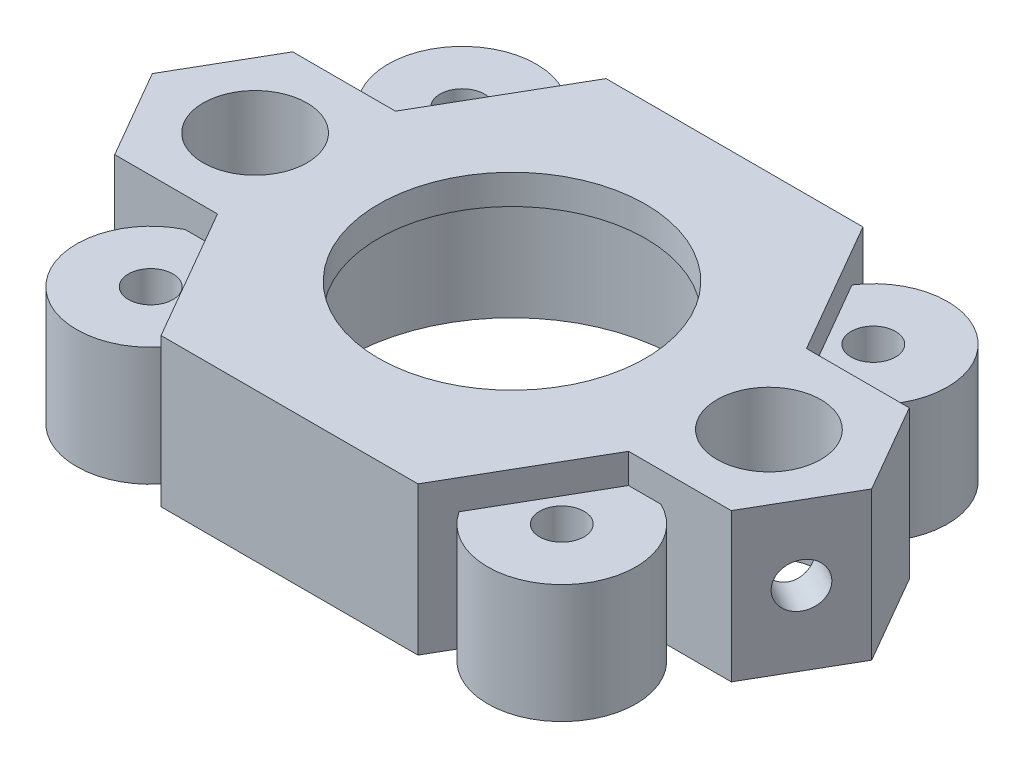
SolidWorks part; units mm, degrees
ref_plane "Front Plane" through (0, 0, 0) normal (0, 0, 1) x (1, 0, 0)
ref_plane "Top Plane" through (0, 0, 0) normal (0, 1, 0) x (1, 0, 0)
ref_plane "Right Plane" through (0, 0, 0) normal (1, 0, 0) x (0, 0, -1)
sketch "Sketch1" plane through (0, 0, 0) normal (0, 1, 0) x (1, 0, 0)
  line L0 (0, 0) -> (17.3205, 0) construction
  line L1 (17.3205, 0) -> (15.5705, 3.0311) construction
  line L2 (8.6603, 15) -> (-8.6603, 15)
  line L3 (-8.6603, 15) -> (-9.6753, 13.2419)
  line L4 (-9.6753, -13.2419) -> (-8.6603, -15)
  line L5 (-8.6603, -15) -> (8.6603, -15)
  line L6 (8.6603, -15) -> (9.6753, -13.2419)
  line L7 (0, 15) -> (0, -15) construction
  line L8 (24.2487, 0) -> (20.7846, 6)
  line L9 (20.7846, 6) -> (16.0359, 6)
  line L10 (12.1244, 3) -> (11.064, 1.1634)
  line L11 (11.064, -1.1634) -> (12.1244, -3) construction
  line L12 (16.0359, -6) -> (20.7846, -6)
  line L13 (20.7846, -6) -> (24.2487, 0)
  line L14 (-20.7846, -6) -> (-24.2487, 0)
  line L15 (-16.0359, -6) -> (-20.7846, -6)
  line L16 (-11.064, -1.1634) -> (-13.8564, -6) construction
  line L17 (-13.8564, 6) -> (-11.064, 1.1634) construction
  line L18 (-20.7846, 6) -> (-16.0359, 6)
  line L19 (-24.2487, 0) -> (-20.7846, 6)
  line L20 (-13.8564, 6) -> (-15.5705, 3.0311) construction
  line L21 (-15.5705, 3.0311) -> (-17.3205, 0) construction
  line L22 (-17.3205, 0) -> (-15.5705, -3.0311) construction
  line L23 (-11.064, 1.1634) -> (-10.3923, 0) construction
  line L24 (-10.3923, 0) -> (-11.064, -1.1634) construction
  line L25 (-15.5705, -3.0311) -> (-13.8564, -6) construction
  line L26 (11.064, 1.1634) -> (10.3923, 0) construction
  line L27 (10.3923, 0) -> (11.064, -1.1634) construction
  line L28 (12.1244, -3) -> (13.8564, -6) construction
  line L29 (15.5705, 3.0311) -> (14.3205, 5.1962) construction
  line L30 (9.6753, 13.2419) -> (8.6603, 15)
  line L31 (14.3205, -5.1962) -> (15.5705, -3.0311) construction
  line L32 (15.5705, -3.0311) -> (17.3205, 0) construction
  line L33 (13.8564, -6) -> (14.3205, -5.1962) construction
  line L34 (13.8564, 6) -> (12.1244, 3) construction
  line L35 (14.3205, 5.1962) -> (13.8564, 6) construction
  line L36 (-13.8564, 6) -> (-13.8564, 15) construction
  line L37 (-13.8564, 15) -> (-8.6603, 15) construction
  line L38 (-9.6753, 13.2419) -> (-13.8564, 6) construction
  line L39 (-16.0359, 6) -> (-13.8564, 6) construction
  line L40 (-55, 0) -> (55, 0) construction
  line L41 (-13.8564, -6) -> (-9.6753, -13.2419) construction
  line L42 (-13.8564, -6) -> (-16.0359, -6) construction
  line L43 (9.6753, -13.2419) -> (13.8564, -6) construction
  line L44 (13.8564, -6) -> (16.0359, -6) construction
  line L45 (16.0359, 6) -> (13.8564, 6) construction
  line L46 (13.8564, 6) -> (9.6753, 13.2419) construction
  line L47 (-17.3205, 0) -> (-8.6603, 15)
  circle A0 centre (0, 0) radius 11.125
  circle A1 centre (0, 0) radius 15 construction
  circle A2 centre (17.3205, 0) radius 3.5
  circle A3 centre (17.3205, 0) radius 6 construction
  circle A4 centre (-17.3205, 0) radius 3.5
  arc A5 (-9.6753, 13.2419) -> (-16.0359, 6) centre (-13.8564, 10.5) ccw
  circle A6 centre (-13.8564, 10.5) radius 1.5
  arc A7 (-13.5724, 5.5081) -> (-9.0703, 11.9469) centre (-13.8564, 10.5) ccw construction
  arc A8 (-9.0703, 11.9469) -> (-9.6753, 13.2419) centre (-13.8564, 10.5) ccw construction
  arc A9 (-13.9549, 5.501) -> (-13.5724, 5.5081) centre (-13.8564, 10.5) ccw construction
  arc A10 (-14.1404, 5.5081) -> (-13.9549, 5.501) centre (-13.8564, 10.5) ccw construction
  arc A11 (-16.0359, 6) -> (-14.1404, 5.5081) centre (-13.8564, 10.5) ccw construction
  circle A12 centre (13.8564, 10.5) radius 1.5
  arc A13 (9.6753, 13.2419) -> (16.0359, 6) centre (13.8564, 10.5) cw
  circle A14 centre (13.8564, -10.5) radius 1.5
  arc A15 (9.6753, -13.2419) -> (16.0359, -6) centre (13.8564, -10.5) ccw
  circle A16 centre (-13.8564, -10.5) radius 1.5
  arc A17 (-9.6753, -13.2419) -> (-16.0359, -6) centre (-13.8564, -10.5) cw
  point P63 (0, 0)
  dimension "D1" = 22.25
  dimension "D3" = 7
  dimension "D6" = 10
  dimension "D7" = 3
  dimension "D2" = 30
  dimension "D4" = 12
  dimension "D5" = 90
extrude "Boss-Extrude1" add sketch "Sketch1" along normal blind 8 contours A6 | A12 | A14 | A16 | L30 L2 L3 A5 L18 L19 L14 L15 A17 L4 L5 L6 A15 L12 L13 L8 L9 A13 | A0 | A4 | A2 region at (-13.8564, 0, -10.5) region at (13.8564, 0, -10.5) region at (13.8564, 0, 10.5) region at (-13.8564, 0, 10.5)
sketch "Sketch2" plane through (0, 8, 0) normal (0, 1, 0) x (1, 0, 0)
  line L1 (8.6603, -15) -> (13.8564, -6)
  line L2 (17.3205, 0) -> (15.5705, 3.0311) construction
  line L3 (8.6603, 15) -> (-8.6603, 15)
  line L4 (-8.6603, 15) -> (-13.8564, 6)
  line L5 (-13.8564, -6) -> (-8.6603, -15)
  line L6 (-8.6603, -15) -> (8.6603, -15)
  line L8 (20.7846, -6) -> (24.2487, 0)
  line L9 (24.2487, 0) -> (20.7846, 6)
  line L10 (20.7846, 6) -> (13.8564, 6)
  line L11 (13.8564, 6) -> (13.7942, 5.8923) construction
  line L12 (10.3923, 0) -> (12.1244, -3) construction
  line L13 (13.8564, -6) -> (20.7846, -6)
  line L15 (-20.7846, -6) -> (-13.8564, -6)
  line L16 (-13.8564, -6) -> (-13.7942, -5.8923) construction
  line L17 (-10.3923, 0) -> (-12.1244, 3) construction
  line L18 (-13.8564, 6) -> (-20.7846, 6)
  line L19 (-20.7846, 6) -> (-24.2487, 0)
  line L20 (-24.2487, 0) -> (-20.7846, -6)
  line L21 (16.0359, -6) -> (20.7846, -6) construction
  line L22 (-16.0359, -6) -> (-20.7846, -6) construction
  line L23 (-14.3205, 5.1962) -> (-15.5705, 3.0311) construction
  line L24 (-15.5705, 3.0311) -> (-17.3205, 0) construction
  line L25 (-17.3205, 0) -> (-15.5705, -3.0311) construction
  line L26 (-15.5705, -3.0311) -> (-14.3205, -5.1962) construction
  line L27 (-14.3205, -5.1962) -> (-13.8564, -6) construction
  line L28 (-13.8564, 6) -> (-14.3205, 5.1962) construction
  line L29 (-12.1244, 3) -> (-13.7942, 5.8923) construction
  line L30 (-13.7942, 5.8923) -> (-13.8564, 6) construction
  line L31 (-12.1244, -3) -> (-10.3923, 0) construction
  line L32 (-13.7942, -5.8923) -> (-12.1244, -3) construction
  line L33 (15.5705, 3.0311) -> (14.3205, 5.1962) construction
  line L34 (13.8564, 6) -> (8.6603, 15)
  line L35 (15.5705, -3.0311) -> (17.3205, 0) construction
  line L36 (14.3205, -5.1962) -> (15.5705, -3.0311) construction
  line L37 (13.8564, -6) -> (14.3205, -5.1962) construction
  line L38 (12.1244, -3) -> (13.7942, -5.8923) construction
  line L39 (13.7942, -5.8923) -> (13.8564, -6) construction
  line L40 (12.1244, 3) -> (10.3923, 0) construction
  line L41 (13.7942, 5.8923) -> (12.1244, 3) construction
  line L42 (14.3205, 5.1962) -> (13.8564, 6) construction
  circle A0 centre (0, 0) radius 9
  circle A1 centre (-17.3205, 0) radius 3.5
  circle A2 centre (17.3205, 0) radius 3.5
  arc A3 (-13.7942, -5.8923) -> (14.1162, 5.0727) centre (0, 0) ccw construction
  circle A4 centre (17.3205, 0) radius 6 construction
  circle A5 centre (-17.3205, 0) radius 3.5 construction
  circle A6 centre (17.3205, 0) radius 3.5 construction
  arc A7 (-14.1162, 5.0727) -> (-14.1162, -5.0727) centre (-17.3205, 0) ccw construction
  arc A8 (-14.1162, -5.0727) -> (-13.7942, -5.8923) centre (0, 0) ccw construction
  arc A9 (-13.7942, 5.8923) -> (-14.1162, 5.0727) centre (0, 0) ccw construction
  arc A10 (-14.1162, 5.0727) -> (-14.1162, -5.0727) centre (0, 0) ccw construction
  arc A11 (-12.1244, 3) -> (-14.1162, 5.0727) centre (-17.3205, 0) ccw construction
  arc A12 (-14.1162, -5.0727) -> (-12.1244, -3) centre (-17.3205, 0) ccw construction
  arc A13 (-12.1244, -3) -> (-12.1244, 3) centre (-17.3205, 0) ccw construction
  arc A14 (14.1162, 5.0727) -> (13.7942, 5.8923) centre (0, 0) ccw construction
  arc A15 (13.7942, 5.8923) -> (-13.7942, 5.8923) centre (0, 0) ccw construction
  dimension "D1" = 18
extrude "Boss-Extrude2" add sketch "Sketch2" along normal blind 2
sketch "Sketch4" plane through (-18.1865, 0, 10.5) normal (-0.866, 0, 0.5) x (0.5, 0, 0.866)
  line L0 (-8.6603, 10) -> (-8.6603, 0) construction
  line L2 (-12.1244, 10) -> (-12.1244, 0) construction
  line L3 (-12.1244, 5) -> (-5.1962, 5) construction
  line L5 (-5.1962, 10) -> (-5.1962, 0) construction
  line L7 (-12.1244, 10) -> (-5.1962, 10) construction
  circle A0 centre (-8.6603, 5) radius 1.5
  point P2 (-8.6603, 10)
  point P3 (-8.6603, 10)
  point P4 (-12.1244, 5)
  point P14 (0, 0)
  dimension "D1" = 3
extrude "Cut-Extrude1" cut sketch "Sketch4" against normal up to surface and the other way through all up to face at (-17.3205, 0, -3.5)
sketch "Sketch5" plane through (18.1865, 0, 10.5) normal (0.866, 0, 0.5) x (0.5, 0, -0.866)
  line L0 (8.6603, 10) -> (8.6603, 0) construction
  line L2 (5.1962, 10) -> (5.1962, 0) construction
  line L3 (5.1962, 5) -> (12.1244, 5) construction
  line L6 (5.1962, 0) -> (12.1244, 0) construction
  circle A0 centre (8.6603, 5) radius 1.5
  point P2 (8.6603, 4)
  point P3 (5.1962, 4)
  point P4 (5.1962, 4)
  point P10 (5.1962, 5)
  point P14 (5.1962, 4)
  point P16 (0, 0)
  dimension "D1" = 3
extrude "Cut-Extrude2" cut sketch "Sketch5" against normal up to surface (2.8377 mm away) up to face at (17.3205, 0, 3.5)
